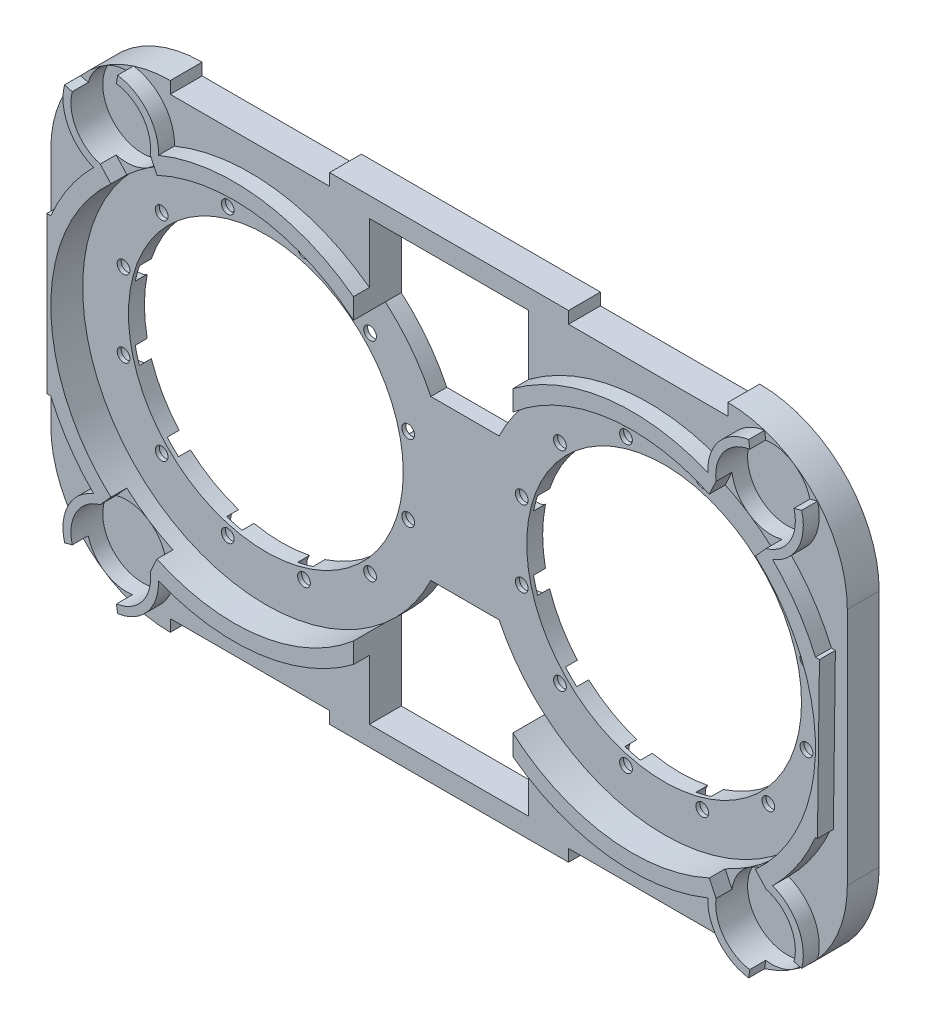
SolidWorks part; units mm, degrees
ref_plane "前视基准面" through (0, 0, 0) normal (0, 0, 1) x (1, 0, 0)
ref_plane "上视基准面" through (0, 0, 0) normal (0, 1, 0) x (1, 0, 0)
ref_plane "右视基准面" through (0, 0, 0) normal (1, 0, 0) x (0, 0, -1)
sketch "草图1" plane through (0, 0, 0) normal (0, 0, 1) x (1, 0, 0)
  line L0 (100, 30) -> (100, -30)
  line L1 (-20, -55) -> (20, -55)
  line L2 (-70, -60) -> (70, -60)
  line L3 (0, -20) -> (-8.5754, -20)
  line L4 (-100, 30) -> (-100, -30)
  line L10 (-70, 60) -> (70, 60)
  line L12 (8.5754, -20) -> (0, -20)
  line L13 (20, -55) -> (20, -34.8712)
  line L14 (-20, -55) -> (-20, -34.8712)
  line L16 (-20, 55) -> (20, 55)
  line L17 (-20, 55) -> (-20, 34.8712)
  line L18 (20, 55) -> (20, 34.8712)
  line L19 (8.5754, 20) -> (0, 20)
  line L20 (0, 20) -> (-8.5754, 20)
  circle A0 centre (-50, 0) radius 34.5
  circle A1 centre (50, 0) radius 34.5
  arc A2 (-100, 30) -> (-70, 60) centre (-70, 30) cw
  arc A3 (-100, -30) -> (-70, -60) centre (-70, -30) ccw
  arc A4 (100, -30) -> (70, -60) centre (70, -30) cw
  arc A5 (100, 30) -> (70, 60) centre (70, 30) ccw
  arc A8 (-8.5754, -20) -> (-20, -34.8712) centre (-50, 0) cw
  arc A9 (8.5754, -20) -> (20, -34.8712) centre (50, 0) ccw
  arc A10 (8.5754, 20) -> (20, 34.8712) centre (50, 0) cw
  arc A11 (-8.5754, 20) -> (-20, 34.8712) centre (-50, 0) ccw
  point P3 (0, -60)
  point P17 (-100, 0)
extrude "面板" add sketch "草图1" against normal blind 4 contours L0 A5 L10 A2 L4 A3 L2 A4 A1 A0 L12 A9 L13 L1 L14 A8 L3 L20 A11 L17 L16 L18 A10 L19 region at (0, 0, 0)
sketch "草图2" plane through (0, 0, 0) normal (0, 0, 1) x (1, 0, 0)
  line L0 (-100, 30) -> (-100, -30)
  line L3 (20, 55) -> (20, 34.8712)
  line L6 (-70, 60) -> (70, 60)
  line L7 (20, 55) -> (-20, 55)
  line L9 (-20, 55) -> (-20, 34.8712)
  line L12 (-70, -60) -> (70, -60)
  line L17 (100, 30) -> (100, -30)
  line L18 (8.5754, 20) -> (-8.5754, 20)
  line L25 (-20, -55) -> (-20, -34.8712)
  line L26 (8.5754, -20) -> (-8.5754, -20)
  line L27 (20, -55) -> (-20, -55)
  line L28 (20, -55) -> (20, -34.8712)
  arc A1 (-100, 30) -> (-70, 60) centre (-70, 30) cw
  arc A2 (-70, 60) -> (-100, 30) centre (-70, 30) ccw construction
  arc A4 (-100, -30) -> (-70, -60) centre (-70, -30) ccw
  arc A5 (100, -30) -> (70, -60) centre (70, -30) cw
  arc A7 (100, 30) -> (70, 60) centre (70, 30) ccw
  circle A20 centre (50, 0) radius 33
  circle A21 centre (-50, 0) radius 33
  arc A22 (8.5754, 20) -> (20, 34.8712) centre (50, 0) cw
  arc A23 (20, 34.8712) -> (8.5754, 20) centre (50, 0) ccw construction
  arc A24 (-8.5754, 20) -> (-20, 34.8712) centre (-50, 0) ccw
  arc A25 (-8.5754, 20) -> (-20, 34.8712) centre (-50, 0) ccw construction
  arc A26 (-8.5754, -20) -> (-20, -34.8712) centre (-50, 0) cw
  arc A27 (8.5754, -20) -> (20, -34.8712) centre (50, 0) ccw
  circle A28 centre (-50, 0) radius 46
  circle A29 centre (50, 0) radius 46
  circle A32 centre (80.95, 46.6721) radius 10
  circle A35 centre (-80.95, 46.6721) radius 10
  circle A36 centre (80.95, -46.6721) radius 10
  circle A37 centre (-80.95, -46.6721) radius 10
extrude "凸台-拉伸1" add sketch "草图2" along normal blind 4 contours L17 A7 L6 A1 L0 A4 L12 A5 A32 A29 A28 L18 A24 L9 L7 L3 A22 L26 A27 L28 L27 L25 A26 A36 A37 region at (-91.0483, 51.0483, 0)
sketch "草图3" plane through (0, 0, 0) normal (0, 0, 1) x (1, 0, 0)
  line L15 (-30, -57) -> (-70, -57)
  line L16 (70, 57) -> (70, 60.1247)
  line L17 (30, 60.1247) -> (30, 57)
  line L18 (70, 60.1247) -> (30, 60.1247)
  line L19 (30, 57) -> (70, 57)
  line L20 (-30, 57) -> (-30, 60)
  line L21 (-70, 60) -> (-30, 60)
  line L22 (-70, 57) -> (-70, 60)
  line L23 (-30, 57) -> (-70, 57)
  line L24 (-70, -57) -> (-70, -60)
  line L25 (-70, -60) -> (-30, -60)
  line L26 (-30, -57) -> (-30, -60)
  line L27 (30, -57) -> (70, -57)
  line L28 (70, -60.1247) -> (30, -60.1247)
  line L29 (30, -60.1247) -> (30, -57)
  line L30 (70, -57) -> (70, -60.1247)
extrude "切除-拉伸1" cut sketch "草图3" against normal blind 4 and the other way blind 4
hole_wizard "M3 六角凹头盖的柱孔2" positions "3D草图3" profile "草图6" counterbore size "M3" standard "BSI" end condition through all
sketch3d "3D草图3"
  point P34 (76.163, 26.163, -4)
  point P36 (59.5763, 35.7393, -4)
  point P38 (59.5763, 35.7393, -4)
  point P40 (40.4237, 35.7393, -4)
  point P42 (23.837, 26.163, -4)
  point P44 (14.2607, 9.5763, -4)
  point P46 (14.2607, -9.5763, -4)
  point P48 (23.837, -26.163, -4)
  point P50 (40.4237, -35.7393, -4)
  point P52 (59.5763, 35.7393, -4)
  point P54 (85.7393, -9.6269, -4)
  point P56 (85.7393, 9.5763, -4)
  point P94 (59.5763, -35.7393, -4)
  point P96 (59.5763, 35.7393, -4)
  point P98 (76.163, -26.163, -4)
  point P157 (-40.4237, 35.7393, -4)
  point P159 (-59.5763, 35.7393, -4)
  point P161 (-76.163, 26.163, -4)
  point P163 (-85.7393, 9.5763, -4)
  point P165 (-85.7393, -9.5763, -4)
  point P167 (-76.163, -26.163, -4)
  point P169 (-59.5763, -35.7393, -4)
  point P171 (-40.4237, -35.7393, -4)
  point P173 (-23.837, -26.163, -4)
  point P175 (-14.2607, -9.5763, -4)
  point P177 (-14.2607, 9.5763, -4)
  point P179 (-23.837, 26.163, -4)
sketch "草图6" plane through (76.163, 26.163, -4) normal (1, 0, 0) x (0, 1, 0)
  line L0 (0, 0) -> (0, 8)
  line L1 (0, 8) -> (1.6, 8)
  line L3 (1.6, 8) -> (1.6, 3)
  line L4 (1.6, 3) -> (3.25, 3)
  line L5 (3.25, 3) -> (3.25, 0)
  line L7 (3.25, 0) -> (0, 0)
  line L11 (0, -6.35) -> (0, 107.95) construction
  dimension "通孔孔直径" = 3.2
  dimension "通孔孔深度" = 8
  dimension "柱形沉头孔直径" = 6.5
  dimension "柱形沉头孔深度" = 3
ref_plane "基准面1" through (0, 0, 4) normal (0, 0, 1) x (1, 0, 0)
sketch "草图7" plane through (0, 0, 4) normal (0, 0, 1) x (1, 0, 0)
  line L8 (-79.2227, -58.5472) -> (-79.5106, -56.568)
  line L9 (-92.5339, 49.8046) -> (-90.6033, 49.2825)
  line L10 (-20, 34.8712) -> (-20, 40)
  line L11 (79.2227, 58.5472) -> (79.5106, 56.568)
  line L13 (-83.5982, 37.0292) -> (-80.9104, 34.0668)
  line L14 (71.0365, 45.3593) -> (69.3536, 41.7305)
  line L15 (-71.0365, 45.3593) -> (-69.3536, 41.7305)
  line L16 (83.5982, 37.0292) -> (80.9104, 34.0668)
  line L18 (20, 34.8712) -> (20, 40)
  line L19 (92.5339, 49.8046) -> (90.6033, 49.2825)
  line L20 (-79.2227, 58.5472) -> (-79.5106, 56.568)
  line L21 (92.5339, -49.8046) -> (90.6033, -49.2825)
  line L22 (20, -34.8712) -> (20, -40)
  line L23 (83.5982, -37.0292) -> (80.9104, -34.0668)
  line L24 (-71.0365, -45.3593) -> (-69.3536, -41.7305)
  line L25 (71.0365, -45.3593) -> (69.3536, -41.7305)
  line L26 (-83.5982, -37.0292) -> (-80.9104, -34.0668)
  line L27 (79.2227, -58.5472) -> (79.5106, -56.568)
  line L28 (-20, -34.8712) -> (-20, -40)
  line L29 (-92.5339, -49.8046) -> (-90.6033, -49.2825)
  line L30 (96, 19.5959) -> (97, 19.5959)
  line L31 (97, 19.5959) -> (96.5, -19.5959)
  line L32 (96.5, -19.5959) -> (96, -19.5959)
  line L33 (-96, 19.5959) -> (-97, 19.5959)
  line L34 (-97, 19.5959) -> (-97, -19.5959)
  line L35 (-97, -19.5959) -> (-96, -19.5959)
  arc A17 (79.5106, 56.568) -> (71.0365, 45.3593) centre (80.95, 46.6721) ccw
  arc A19 (20, 34.8712) -> (69.3536, 41.7305) centre (50, 0) cw
  arc A20 (20, 40) -> (68.9568, 46.267) centre (50, 0) cw
  arc A21 (96, 19.5959) -> (85.2437, 35.4666) centre (50, 0) ccw
  arc A22 (-80.9104, 34.0668) -> (-80.9104, -34.0668) centre (-50, 0) ccw
  arc A24 (90.6033, 49.2825) -> (83.5982, 37.0292) centre (80.95, 46.6721) cw
  arc A25 (79.2227, 58.5472) -> (68.9568, 46.267) centre (80.95, 46.6721) ccw
  arc A26 (100, 30) -> (70, 60) centre (70, 30) ccw construction
  arc A27 (92.5339, 49.8046) -> (85.2437, 35.4666) centre (80.95, 46.6721) cw
  arc A28 (80.9104, 34.0668) -> (80.9104, -34.0668) centre (50, 0) cw
  arc A29 (-92.5339, 49.8046) -> (-85.2437, 35.4666) centre (-80.95, 46.6721) ccw
  arc A30 (-79.2227, 58.5472) -> (-68.9568, 46.267) centre (-80.95, 46.6721) cw
  arc A31 (-90.6033, 49.2825) -> (-83.5982, 37.0292) centre (-80.95, 46.6721) ccw
  arc A32 (-96, 19.5959) -> (-85.2437, 35.4666) centre (-50, 0) cw
  arc A33 (-20, 40) -> (-68.9568, 46.267) centre (-50, 0) ccw
  arc A34 (-20, 34.8712) -> (-69.3536, 41.7305) centre (-50, 0) ccw
  arc A35 (-79.5106, 56.568) -> (-71.0365, 45.3593) centre (-80.95, 46.6721) cw
  arc A36 (-79.5106, -56.568) -> (-71.0365, -45.3593) centre (-80.95, -46.6721) ccw
  arc A37 (-20, -34.8712) -> (-69.3536, -41.7305) centre (-50, 0) cw
  arc A38 (-20, -40) -> (-68.9568, -46.267) centre (-50, 0) cw
  arc A39 (-96, -19.5959) -> (-85.2437, -35.4666) centre (-50, 0) ccw
  arc A40 (-90.6033, -49.2825) -> (-83.5982, -37.0292) centre (-80.95, -46.6721) cw
  arc A41 (-79.2227, -58.5472) -> (-68.9568, -46.267) centre (-80.95, -46.6721) ccw
  arc A42 (-92.5339, -49.8046) -> (-85.2437, -35.4666) centre (-80.95, -46.6721) cw
  arc A43 (92.5339, -49.8046) -> (85.2437, -35.4666) centre (80.95, -46.6721) ccw
  arc A44 (79.2227, -58.5472) -> (68.9568, -46.267) centre (80.95, -46.6721) cw
  arc A45 (90.6033, -49.2825) -> (83.5982, -37.0292) centre (80.95, -46.6721) ccw
  arc A46 (96, -19.5959) -> (85.2437, -35.4666) centre (50, 0) cw
  arc A47 (20, -40) -> (68.9568, -46.267) centre (50, 0) ccw
  arc A48 (20, -34.8712) -> (69.3536, -41.7305) centre (50, 0) ccw
  arc A49 (79.5106, -56.568) -> (71.0365, -45.3593) centre (80.95, -46.6721) cw
  point P7 (96, 0)
  point P70 (-96, 0)
extrude "凸台-拉伸9" add sketch "草图7" along normal blind 4
